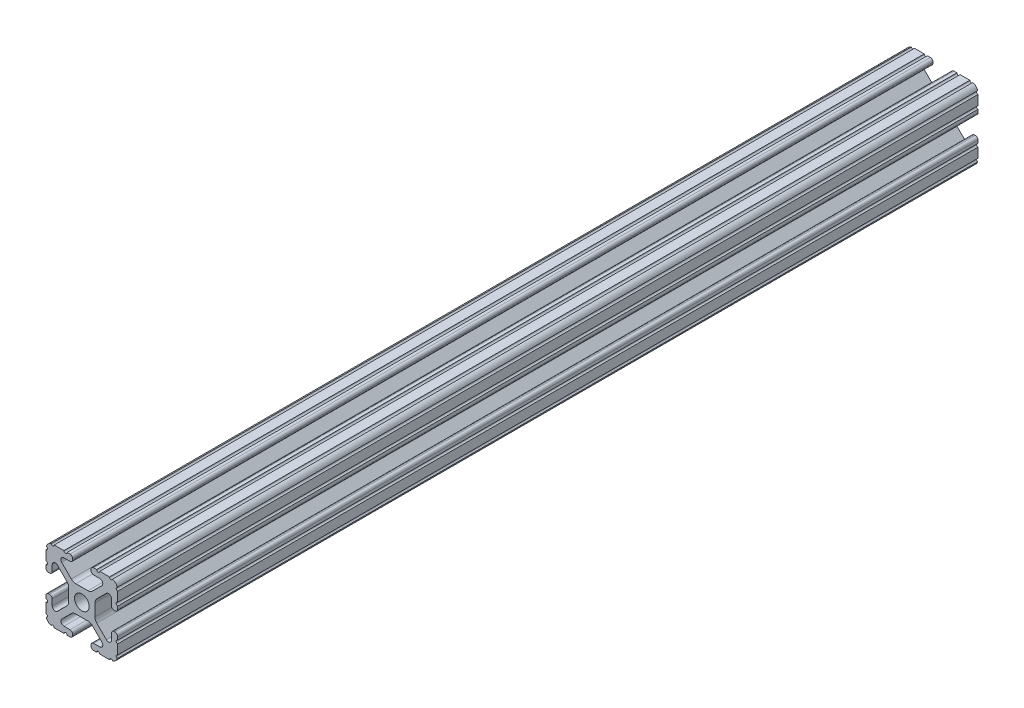
SolidWorks part; units mm, degrees
ref_plane "Front Plane" through (0, 0, 0) normal (0, 0, 1) x (1, 0, 0)
ref_plane "Top Plane" through (0, 0, 0) normal (0, 1, 0) x (1, 0, 0)
ref_plane "Right Plane" through (0, 0, 0) normal (1, 0, 0) x (0, 0, -1)
sketch "Sketch2" plane through (0, 0, 0) normal (0, 0, 1) x (1, 0, 0)
  line L0 (0, 12.7) -> (0, -12.7) construction
  line L1 (-12.7, 0) -> (12.7, 0) construction
  line L2 (3.2512, -12.7) -> (12.7, -12.7)
  line L3 (12.7, -12.7) -> (12.7, -3.2512)
  line L4 (3.2512, -12.7) -> (3.2512, -10.4902)
  line L5 (3.2512, -10.4902) -> (8.9276, -10.4902)
  line L6 (8.9276, -10.4902) -> (3.0856, -4.6482)
  line L7 (0, 0) -> (12.7, -12.7) construction
  line L8 (12.7, -3.2512) -> (10.4902, -3.2512)
  line L9 (10.4902, -3.2512) -> (10.4902, -8.9276)
  line L10 (10.4902, -8.9276) -> (4.6482, -3.0856)
  circle A0 centre (0, 0) radius 2.6035
  arc A1 (6.3485, -10.4902) -> (7.1039, -8.6665) centre (6.3485, -9.4219) ccw construction
  point P8 (0, -4.6482)
  dimension "Center Hole Diameter" = 5.207
  dimension "Rail Height" = 25.4
  dimension "Rail Width" = 25.4
  dimension "T-Slot Width" = 6.5024
  dimension "Slot Inner Width" = 14.8336
  dimension "Thickness" = 2.2098
  dimension "Slot Depth" = 5.842
  dimension "D1" = 2.2098
sketch "Sketch3" plane through (0, 0, 0) normal (1, 0, 0) x (0, 0, -1)
  line L0 (-304.8, -12.7) -> (304.8, -12.7) construction
  line L1 (-279.4, 0) -> (279.4, 0) construction
  dimension "Length" = 609.6
  dimension "D1" = 25.4
sketch "Sketch4" plane through (0, 0, 0) normal (0, 0, 1) x (1, 0, 0)
  line L0 (4.1904, -12.7) -> (10.1173, -12.7)
  line L1 (3.2512, -12.7) -> (12.7, -12.7) construction
  line L2 (3.2512, -12.7) -> (3.2512, -10.4902) construction
  line L3 (3.2512, -10.4902) -> (8.9276, -10.4902) construction
  line L4 (3.2512, -11.4294) -> (3.2512, -11.7608)
  line L5 (4.1904, -10.4902) -> (6.3485, -10.4902)
  line L6 (0, -4.6482) -> (2.164, -4.6482)
  line L7 (8.9276, -10.4902) -> (3.0856, -4.6482) construction
  line L8 (3.7373, -5.2999) -> (7.1039, -8.6665)
  line L9 (12.7, -12.7) -> (12.7, -3.2512) construction
  line L10 (10.4902, -8.9276) -> (4.6482, -3.0856) construction
  line L11 (10.4902, -3.2512) -> (10.4902, -8.9276) construction
  line L12 (10.4902, -6.3485) -> (10.4902, -4.1904)
  line L13 (12.7, -3.2512) -> (10.4902, -3.2512) construction
  line L14 (11.4294, -3.2512) -> (11.7608, -3.2512)
  line L15 (12.7, -4.1904) -> (12.7, -10.1173)
  line L16 (8.6665, -7.1039) -> (5.2999, -3.7373)
  line L17 (4.6482, 0) -> (4.6482, -2.164)
  line L18 (-12.7, 0) -> (12.7, 0) construction
  line L19 (0, -4.6482) -> (0, -2.6035)
  line L20 (0, 12.7) -> (0, -12.7) construction
  line L21 (4.6482, 0) -> (2.6035, 0)
  arc A0 (3.2512, -11.7608) -> (4.1904, -12.7) centre (4.1904, -11.7608) ccw
  arc A2 (3.2512, -11.4294) -> (4.1904, -10.4902) centre (4.1904, -11.4294) cw
  arc A3 (6.3485, -10.4902) -> (7.1039, -8.6665) centre (6.3485, -9.4219) ccw
  arc A4 (2.164, -4.6482) -> (3.7373, -5.2999) centre (2.164, -6.8732) cw
  arc A5 (10.1173, -12.7) -> (12.7, -10.1173) centre (10.1173, -10.1173) ccw
  arc A6 (8.6665, -7.1039) -> (10.4902, -6.3485) centre (9.4219, -6.3485) ccw
  arc A7 (10.4902, -4.1904) -> (11.4294, -3.2512) centre (11.4294, -4.1904) cw
  arc A8 (11.7608, -3.2512) -> (12.7, -4.1904) centre (11.7608, -4.1904) cw
  arc A9 (5.2999, -3.7373) -> (4.6482, -2.164) centre (6.8732, -2.164) cw
  circle A10 centre (0, 0) radius 2.6035 construction
  arc A11 (0, -2.6035) -> (2.6035, 0) centre (0, 0) ccw
  dimension "D1" = 2.5827
  dimension "D2" = 2.225
  dimension "D3" = 0.9392
extrude "Boss-Extrude1" add sketch "Sketch4" along normal mid plane 609.6
sketch "Sketch5" plane through (0, 0, 0) normal (0, 0, 1) x (1, 0, 0)
  line L0 (3.2512, -12.7) -> (12.7, -12.7) construction
  line L1 (4.1904, -10.4902) -> (6.3485, -10.4902) construction
  line L3 (0, 0) -> (12.7, -12.7) construction
  line L4 (6.3485, -10.4902) -> (6.3485, -12.7) construction
  line L5 (8.9276, -10.4902) -> (3.0856, -4.6482) construction
  circle A0 centre (10.3562, -12.7) radius 0.5524
  circle A1 centre (5.796, -12.7) radius 0.5524
  circle A2 centre (12.7, -10.3562) radius 0.5524
  circle A3 centre (12.7, -5.796) radius 0.5524
  point P10 (5.2694, -10.4902)
  point P12 (9.4219, -6.3485)
  dimension "D1" = 1.1049
extrude "Cut-Extrude1" cut sketch "Sketch5" against normal through all both and the other way through all
mirror "Mirror1" about plane through (0, 0, 0) normal (1, 0, 0) of bodies 137 134
mirror "Mirror2" about plane through (0, 0, 0) normal (0, 1, 0) of bodies 135
sketch "Sketch6" plane through (0, 0, -304.8) normal (0, 0, -1) x (-1, 0, 0)
  line L1 (-37.9045, 25.7252) -> (35.4927, 25.7252)
  line L2 (-37.9045, 25.7252) -> (-37.9045, -23.1527)
  line L3 (-37.9045, -23.1527) -> (35.4927, -23.1527)
  line L4 (35.4927, 25.7252) -> (35.4927, -23.1527)
  point P4 (35.4927, -23.1527)
extrude "Cut-Extrude2" cut sketch "Sketch6" against normal blind 304.8
equation "\"D1@Boss-Extrude1\"=\"Length@Sketch3\""
equation "\"D1@Sketch2\"=\"Thickness@Sketch2\""
equation "\"D2@Sketch4\"=\"Slot Inner Width@Sketch2\"*0.15"
equation "\"D1@Sketch4\"=\"D3@Sketch4\"*2.75"
equation "\"D3@Sketch4\"=\"Thickness@Sketch2\"*0.425"
equation "\"D1@Sketch5\"=\"Thickness@Sketch2\"*0.5"
